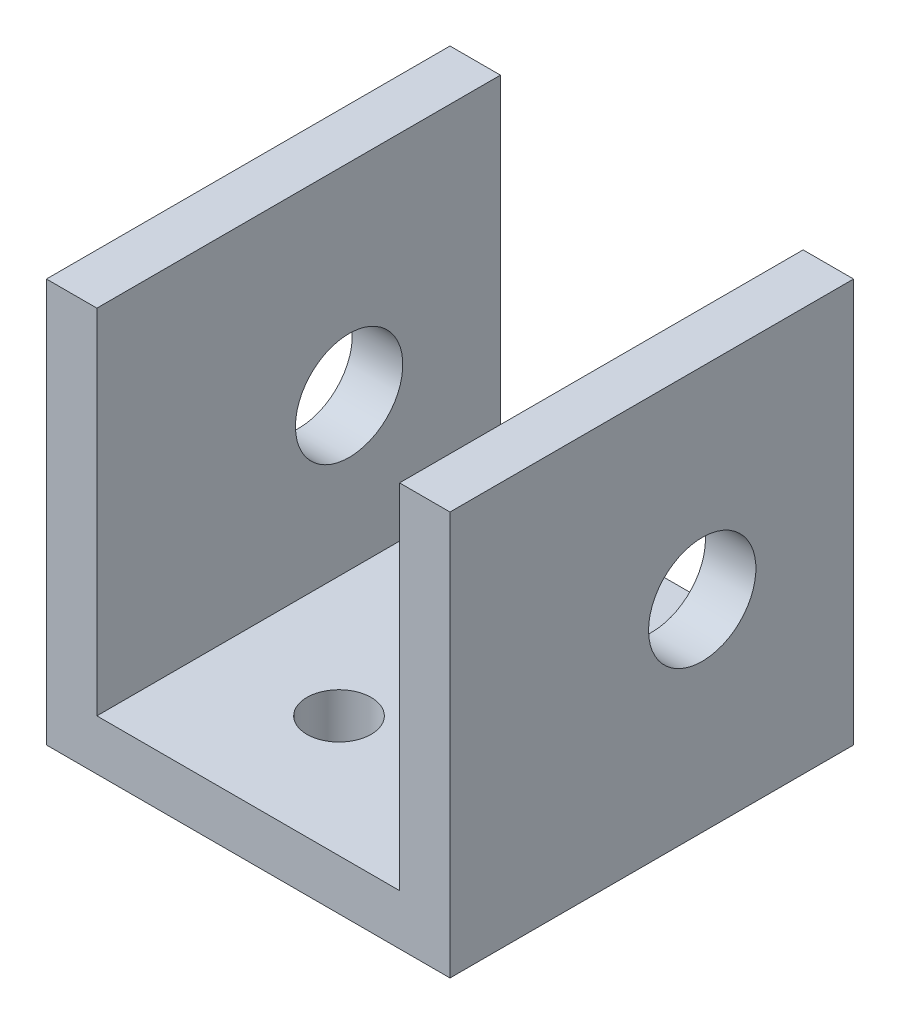
SolidWorks part; units mm, degrees
material "6061-T6 (SS)"
ref_plane "Front" through (0, 0, 0) normal (0, 0, 1) x (1, 0, 0)
ref_plane "Top" through (0, 0, 0) normal (0, 1, 0) x (1, 0, 0)
ref_plane "Right" through (0, 0, 0) normal (1, 0, 0) x (0, 0, -1)
sketch "Sketch1" plane through (0, 0, 0) normal (0, 1, 0) x (1, 0, 0)
  line L1 (-12.7, -12.7) -> (12.7, -12.7)
  line L2 (-12.7, -12.7) -> (-12.7, 12.7)
  line L3 (-12.7, 12.7) -> (12.7, 12.7)
  line L4 (12.7, -12.7) -> (12.7, 12.7)
  line L5 (-12.7, -12.7) -> (12.7, 12.7) construction
  line L6 (-12.7, 12.7) -> (12.7, -12.7) construction
  point P0 (0, 0)
  dimension "D1" = 25.4
  dimension "D2" = 25.4
extrude "Boss-Extrude1" add sketch "Sketch1" along normal blind 3.175
sketch "Sketch2" plane through (0, 3.175, 0) normal (0, 1, 0) x (1, 0, 0)
  line L0 (-12.7, 12.7) -> (-12.7, -12.7)
  line L1 (-12.7, -12.7) -> (-9.525, -12.7)
  line L2 (-12.7, -12.7) -> (12.7, -12.7) construction
  line L3 (-9.525, -12.7) -> (-9.525, 12.7)
  line L4 (12.7, 12.7) -> (-12.7, 12.7) construction
  line L5 (-9.525, 12.7) -> (-12.7, 12.7)
  line L6 (12.7, 12.7) -> (9.525, 12.7)
  line L7 (9.525, 12.7) -> (9.525, -12.7)
  line L8 (9.525, -12.7) -> (12.7, -12.7)
  line L9 (12.7, -12.7) -> (12.7, 12.7)
  dimension "D1" = 3.175
extrude "Boss-Extrude2" add sketch "Sketch2" along normal blind 22.225
sketch "Sketch6" plane through (0, 3.175, 0) normal (0, 1, 0) x (1, 0, 0)
  line L0 (9.525, 12.7) -> (-9.525, 12.7) construction
  line L1 (9.525, 12.7) -> (9.525, -12.7) construction
  line L2 (-9.525, -12.7) -> (-9.525, 12.7) construction
  line L3 (-9.525, -12.7) -> (9.525, -12.7) construction
  point P0 (1.905, 5.08)
  point P2 (-1.905, -5.08)
  dimension "D1" = 7.62
  dimension "D2" = 7.62
  dimension "D3" = 7.62
  dimension "D4" = 7.62
hole_wizard "#10-32 Tapped Hole1" positions "Sketch6" profile "Sketch5" tap size "#10-32" standard "ANSI Inch" end condition through all
sketch "Sketch5" plane through (1.905, 3.175, -5.08) normal (1, 0, 0) x (0, 0, 1)
  line L0 (0, 0) -> (0, 3.175)
  line L1 (0, 3.175) -> (2.0193, 3.175)
  line L2 (2.0193, 3.175) -> (2.0193, 0)
  line L5 (2.0193, 0) -> (0, 0)
  line L11 (0, -6.35) -> (0, 107.95) construction
  dimension "Thru Tap Drill Dia." = 4.0386
  dimension "Thru Tap Drill Depth" = 3.175
sketch "Sketch9" plane through (-12.7, 0, 0) normal (-1, 0, 0) x (0, 0, 1)
  line L0 (-12.7, 25.4) -> (12.7, 25.4) construction
  line L1 (-12.7, 25.4) -> (-12.7, 0) construction
  point P0 (-3.175, 12.7)
  dimension "D1" = 12.7
  dimension "D2" = 9.525
hole_wizard "1/4 Clearance Hole1" positions "Sketch9" profile "Sketch8" hole size "1/4" standard "ANSI Inch" end condition through all
sketch "Sketch8" plane through (-12.7, 12.7, -3.175) normal (0, 1, 0) x (0, 0, 1)
  line L0 (0, 0) -> (0, 25.4)
  line L1 (0, 25.4) -> (3.3782, 25.4)
  line L2 (3.3782, 25.4) -> (3.3782, 0)
  line L5 (3.3782, 0) -> (0, 0)
  line L11 (0, -6.35) -> (0, 107.95) construction
  dimension "Thru Hole Dia." = 6.7564
  dimension "Thru Hole Depth" = 25.4
